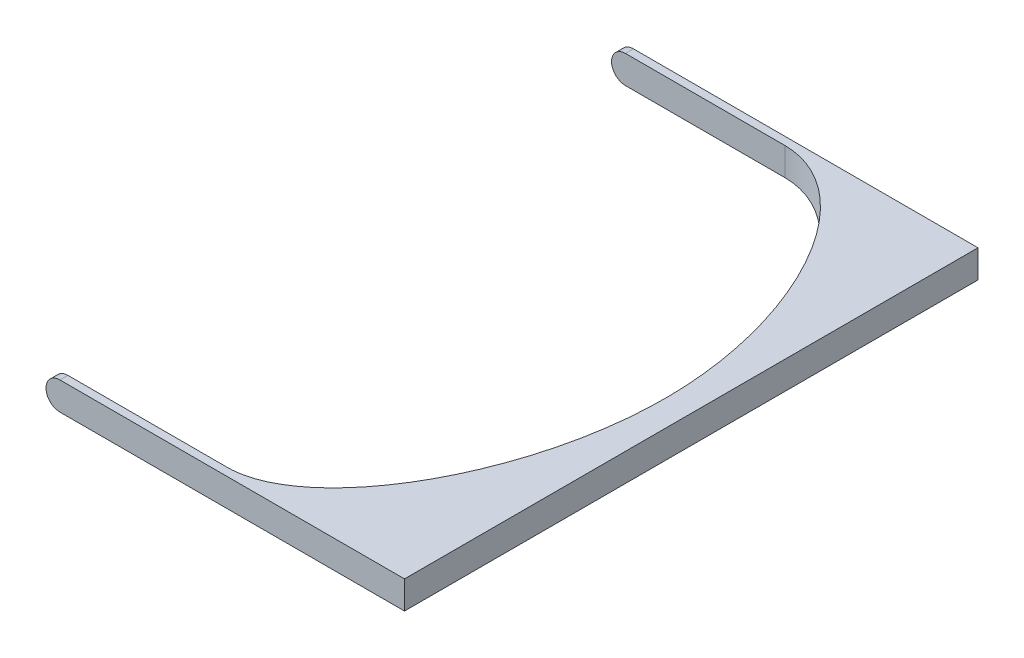
SolidWorks part; units mm, degrees
ref_plane "Front Plane" through (0, 0, 0) normal (0, 0, 1) x (1, 0, 0)
ref_plane "Top Plane" through (0, 0, 0) normal (0, 1, 0) x (1, 0, 0)
ref_plane "Right Plane" through (0, 0, 0) normal (1, 0, 0) x (0, 0, -1)
sketch "Sketch1" plane through (0, 0, 0) normal (0, 0, 1) x (1, 0, 0)
  line L0 (0, 8.89) -> (219.7515, 8.89)
  line L1 (219.7515, 8.89) -> (219.7515, -8.89)
  line L2 (219.7515, -8.89) -> (0, -8.89)
  circle A0 centre (0, 0) radius 3.81
  arc A1 (0, 8.89) -> (0, -8.89) centre (0, 0) ccw
  circle A3 centre (0, 0) radius 8.89 construction
  point P7 (8.89, 0)
  dimension "D1" = 7.62
  dimension "D3" = 219.7515
  dimension "D2" = 5.08
extrude "Boss-Extrude1" add sketch "Sketch1" along normal blind 182.88 and the other way blind 182.88 contours L0 L1 L2 A1
extrude "Cut-Extrude1" cut sketch "Sketch1<5>" against normal blind 177.8 and the other way blind 177.8 flip side to cut
sketch "Sketch1<5>" plane through (0, 0, 0) normal (0, 0, 1) x (1, 0, 0) same geometry as "Sketch1"
sketch "Sketch3" plane through (0, 0, 0) normal (0, 1, 0) x (1, 0, 0)
  line L1 (-101.6, 177.8) -> (101.6, 177.8)
  line L2 (-101.6, 177.8) -> (-101.6, -177.8)
  line L3 (-101.6, -177.8) -> (101.6, -177.8)
  line L4 (101.6, 177.8) -> (101.6, -177.8) construction
  line L5 (-101.6, 177.8) -> (101.6, -177.8) construction
  line L6 (-101.6, -177.8) -> (101.6, 177.8) construction
  line L7 (-9.779, 0) -> (9.779, 0) construction
  spline S0 degree 3 poles (101.6, 177.8) (152.4, 177.8) (254, 0) (152.4, -177.8) (101.6, -177.8) knots 0 0 0 0 0.5 1 1 1 1
  point P0 (0, 0)
  dimension "D3" = 152.4
  dimension "D4" = 152.4
  dimension "D1" = 355.6
  dimension "D2" = 203.2
extrude "Cut-Extrude2" cut sketch "Sketch3" against normal through all and the other way through all contours L1 S0 L3 L2
